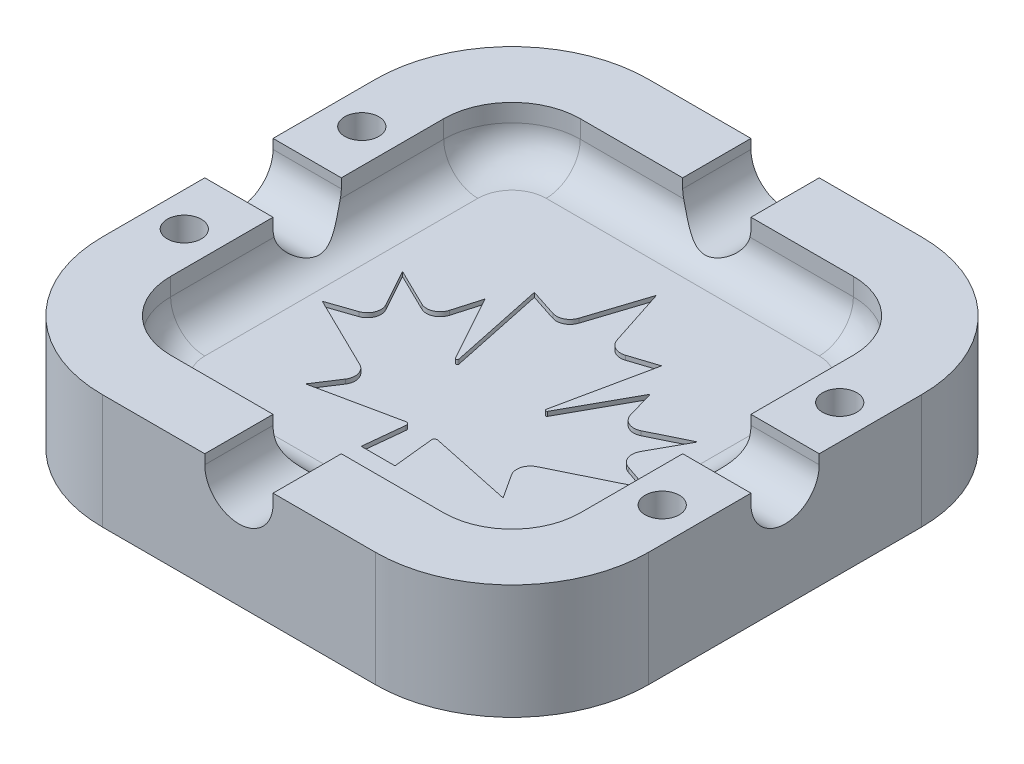
SolidWorks part; units mm, degrees
ref_plane "Front" through (0, 0, 0) normal (0, 0, 1) x (1, 0, 0)
ref_plane "Top" through (0, 0, 0) normal (0, 1, 0) x (1, 0, 0)
ref_plane "Side" through (0, 0, 0) normal (1, 0, 0) x (0, 0, -1)
sketch "MCAM Cord system" plane through (0, 0, 0) normal (0, 0, 1) x (1, 0, 0)
  line L0 (0, 0) -> (0, 32.3125) construction
  line L1 (0, 0) -> (36.1919, 0) construction
sketch "Sketch1" plane through (0, 0, 0) normal (0, 1, 0) x (1, 0, 0)
  line L0 (-25.4, 25.4) -> (25.4, -25.4) construction
  line L1 (-25.4, 25.4) -> (25.4, 25.4)
  line L2 (-25.4, 25.4) -> (-25.4, -25.4)
  line L3 (-25.4, -25.4) -> (25.4, -25.4)
  line L4 (25.4, 25.4) -> (25.4, -25.4)
  point P12 (25.4, 25.4)
  dimension "D2" = 50.8
  dimension "D1" = 50.8
extrude "Boss-Extrude1" add sketch "Sketch1" against normal blind 10.668
sketch "Sketch3" plane through (0, 0, 0) normal (0, 1, 0) x (1, 0, 0)
  line L8 (19.05, -19.05) -> (19.05, 19.05)
  line L9 (19.05, 19.05) -> (-19.05, 19.05)
  line L10 (-19.05, 19.05) -> (-19.05, -19.05)
  line L11 (-19.05, -19.05) -> (19.05, -19.05)
  line L12 (19.05, -12.7) -> (19.05, 12.7)
  line L13 (12.7, 19.05) -> (-12.7, 19.05)
  line L14 (-19.05, 12.7) -> (-19.05, -12.7)
  line L15 (-12.7, -19.05) -> (12.7, -19.05)
  arc A4 (-19.05, -12.7) -> (-12.7, -19.05) centre (-12.7, -12.7) ccw
  arc A5 (19.05, -12.7) -> (12.7, -19.05) centre (12.7, -12.7) cw
  arc A6 (19.05, 12.7) -> (12.7, 19.05) centre (12.7, 12.7) ccw
  arc A7 (-12.7, 19.05) -> (-19.05, 12.7) centre (-12.7, 12.7) ccw
  dimension "D2" = 6.35
  dimension "D1" = 6.35
extrude "Cut-Extrude2" cut sketch "Sketch3" against normal blind 4.826
fillet "Fillet2" radius 12.7 4 edges at (25.4, -5.334, -25.4) (25.4, -5.334, 25.4) (-25.4, -5.334, 25.4) (-25.4, -5.334, -25.4)
fillet "Fillet1" radius 3.175 8 edges at (17.1901, -4.826, -17.1901) (19.05, -4.826, 0) (17.1901, -4.826, 17.1901) (0, -4.826, 19.05) (-17.1901, -4.826, 17.1901) (-19.05, -4.826, 0) (-17.1901, -4.826, -17.1901) (0, -4.826, -19.05)
sketch "Sketch4" plane through (0, 0, 0) normal (1, 0, 0) x (0, 0, -1)
  line L2 (-3.175, -0.889) -> (-3.175, 0)
  line L4 (-12.7, 0) -> (12.7, 0) construction
  line L5 (3.175, -0.889) -> (3.175, 0)
  line L6 (3.175, 0) -> (-3.175, 0)
  line L7 (0, -4.064) -> (7.4473, -4.064) construction
  arc A0 (-3.175, -0.889) -> (3.175, -0.889) centre (0, -0.889) ccw
  dimension "D1" = 4.064
  dimension "D2" = 6.35
extrude "Cut-Extrude3" cut sketch "Sketch4" against normal mid plane 59.944
ref_axis "Axis1" through (0, 50, 0) along (0, -1, 0)
pattern_circular "CirPattern1" count 4 over 360 about axis through (0, 50, 0) along (0, -1, 0) of "Cut-Extrude3"
sketch "Sketch5" plane through (0, -4.826, 0) normal (0, 1, 0) x (1, 0, 0)
  text T0 "UWO\r\nUMS"
extrude "Cut-Extrude4 UWO UMS engrave" [suppressed] cut sketch "Sketch5" against normal blind 0.7874
hole_wizard "1/8 (0.125) Diameter Hole1" positions "Sketch7" profile "Sketch6" hole size "1/8" standard "ANSI Inch"
sketch "Sketch7" plane through (0, 0, 0) normal (0, 1, 0) x (-1, 0, 0)
  line L2 (0, 0) -> (35.8085, 0) construction
  line L4 (0, 0) -> (0, -33.2213) construction
  line L5 (25.4, -12.7) -> (25.4, -3.175) construction
  line L6 (25.4, -3.175) -> (19.05, -3.175) construction
  point P0 (22.225, -8.255)
  point P21 (22.225, 8.255)
  point P23 (-22.225, 8.255)
  point P24 (-22.225, -8.255)
  dimension "D1" = 3.175
  dimension "D2" = 5.08
sketch "Sketch6" plane through (-22.225, 0, -8.255) normal (1, 0, 0) x (0, 0, 1)
  line L0 (0, 0) -> (0, 5.2719)
  line L1 (0, 5.2719) -> (1.5875, 4.318)
  line L2 (1.5875, 4.318) -> (1.5875, 0)
  line L5 (1.5875, 0) -> (0, 0)
  line L10 (0, 5.2719) -> (-1.5875, 4.318) construction
  line L11 (0, -6.35) -> (0, 107.95) construction
  dimension "Hole Dia." = 3.175
  dimension "Hole Depth" = 4.318
  dimension "Drill Angle" = 118
sketch "Sketch9" plane through (0, -4.826, 0) normal (0, 1, 0) x (1, 0, 0)
  line L0 (0.246, 15.3092) -> (0.246, -18.2427) construction
  line L1 (0.246, 13.1897) -> (-1.5247, 7.7402)
  line L2 (-12.7, -25.4) -> (-3.175, -25.4) construction
  line L3 (-3.125, 6.9248) -> (-5.6734, 7.7528)
  line L4 (-5.6734, 7.7528) -> (-3.8057, -1.1208)
  line L5 (-4.0412, -1.2084) -> (-7.4307, 4.9339)
  line L6 (-7.4307, 4.9339) -> (-8.1741, 2.3596)
  line L7 (-9.9532, 1.5716) -> (-13.4884, 3.3041)
  line L8 (-13.4884, 3.3041) -> (-11.5862, -0.1428)
  line L9 (-12.287, -1.958) -> (-14.8221, -2.8256)
  line L10 (-14.8221, -2.8256) -> (-7.9797, -6.1789)
  line L11 (-7.4748, -8.0131) -> (-8.9384, -10.2575)
  line L12 (-8.9384, -10.2575) -> (-1.2332, -8.6358)
  line L13 (-0.9283, -8.9109) -> (-1.3265, -12.7)
  line L14 (-1.3265, -12.7) -> (1.8185, -12.7)
  line L15 (1.4202, -8.9109) -> (1.8185, -12.7)
  line L16 (9.4303, -10.2575) -> (1.7251, -8.6358)
  line L17 (7.9667, -8.0131) -> (9.4303, -10.2575)
  line L18 (15.3141, -2.8256) -> (8.4716, -6.1789)
  line L19 (12.7789, -1.958) -> (15.3141, -2.8256)
  line L20 (13.9803, 3.3041) -> (12.0782, -0.1428)
  line L21 (10.4451, 1.5716) -> (13.9803, 3.3041)
  line L22 (7.9226, 4.9339) -> (8.6661, 2.3596)
  line L23 (4.5331, -1.2084) -> (7.9226, 4.9339)
  line L24 (6.1653, 7.7528) -> (4.2976, -1.1208)
  line L25 (3.6169, 6.9248) -> (6.1653, 7.7528)
  line L26 (0.246, 13.1897) -> (2.0166, 7.7402)
  arc A0 (-1.5247, 7.7402) -> (-3.125, 6.9248) centre (-2.7325, 8.1326) cw
  arc A1 (-7.9797, -6.1789) -> (-7.4748, -8.0131) centre (-8.5386, -7.3193) cw
  arc A2 (-11.5862, -0.1428) -> (-12.287, -1.958) centre (-12.6982, -0.7564) cw
  arc A3 (-8.1741, 2.3596) -> (-9.9532, 1.5716) centre (-9.3943, 2.712) cw
  arc A4 (-3.8057, -1.1208) -> (-4.0412, -1.2084) centre (-3.93, -1.147) cw
  arc A5 (-0.9283, -8.9109) -> (-1.2332, -8.6358) centre (-1.1809, -8.8843) ccw
  arc A6 (1.4202, -8.9109) -> (1.7251, -8.6358) centre (1.6728, -8.8843) cw
  arc A7 (4.2976, -1.1208) -> (4.5331, -1.2084) centre (4.4219, -1.147) ccw
  arc A8 (8.6661, 2.3596) -> (10.4451, 1.5716) centre (9.8862, 2.712) ccw
  arc A9 (12.0782, -0.1428) -> (12.7789, -1.958) centre (13.1901, -0.7564) ccw
  arc A10 (8.4716, -6.1789) -> (7.9667, -8.0131) centre (9.0305, -7.3193) ccw
  arc A11 (2.0166, 7.7402) -> (3.6169, 6.9248) centre (3.2245, 8.1326) ccw
  point P17 (-1.9172, 6.5323)
  point P51 (0.246, -12.7)
  point P56 (2.4091, 6.5323)
  dimension "D6" = 1.27
  dimension "D7" = 1.27
  dimension "D8" = 1.27
  dimension "D9" = 1.27
  dimension "D10" = 0.127
  dimension "D11" = 0.254
  dimension "D1" = 18
  dimension "D2" = 7
  dimension "D3" = 80
  dimension "D4" = 80
  dimension "D5" = 35
  dimension "D12" = 12.7
  dimension "D13" = 6
  dimension "D14" = 3.81
  dimension "D15" = 7.874
  dimension "D16" = 83
extrude "Cut-Extrude4" cut sketch "Sketch9" against normal blind 0.4064
sketch "Sketch20" plane through (0, -10.668, 0) normal (0, -1, 0) x (-1, 0, 0)
  line L0 (-18.5358, -7.366) -> (18.5358, -7.366) construction
  line L1 (-8.4009, 7.4831) -> (-5.7011, 16.3751)
  line L2 (-9.2516, 6.8524) -> (9.1902, 6.8524) construction
  line L3 (-9.0426, -20.32) -> (9.0426, -20.32) construction
  line L4 (0, -20.32) -> (0, -7.366) construction
  line L22 (12.7, -25.4) -> (-12.7, -25.4) construction
  line L23 (-5.7011, 16.3751) -> (-3.0053, 7.4766)
  line L25 (-1.2647, 7.7348) -> (-1.2647, 19.431)
  line L26 (0, -20.32) -> (0, -25.4) construction
  line L27 (-3.0427, 19.431) -> (-3.0447, 13.7331)
  line L28 (-3.0447, 13.7331) -> (-4.854, 19.6957)
  line L29 (-6.5513, 19.6958) -> (-8.3605, 13.7331)
  line L30 (-8.3605, 13.7331) -> (-8.3605, 19.4377)
  line L31 (-10.1385, 19.4377) -> (-10.1406, 7.7415)
  line L32 (9.1908, 8.6304) -> (3.1034, 8.6325)
  line L33 (3.1034, 8.6325) -> (3.1048, 12.7026)
  line L34 (3.1048, 12.7026) -> (9.1923, 12.7005)
  line L35 (9.1929, 14.4785) -> (3.1054, 14.4806)
  line L36 (3.1054, 14.4806) -> (3.1069, 18.542)
  line L37 (3.1069, 18.542) -> (9.1301, 18.542)
  line L38 (9.1301, 20.32) -> (1.8788, 20.32)
  line L39 (1.2338, 19.6718) -> (1.2955, 7.4941)
  line L40 (1.9405, 6.8524) -> (9.1902, 6.8524)
  line L41 (-1.2647, 13.5829) -> (1.2647, 13.5829) construction
  line L42 (0, 13.5829) -> (0, 0) construction
  line L43 (-9.2495, 20.32) -> (9.1301, 20.32) construction
  line L44 (1.2338, 20.32) -> (1.2338, 25.4) construction
  line L45 (-12.7, 25.4) -> (12.7, 25.4) construction
  arc A0 (-3.0053, 7.4766) -> (-1.2647, 7.7348) centre (-2.1537, 7.7317) ccw
  arc A11 (-1.2647, 19.431) -> (-3.0427, 19.431) centre (-2.1537, 19.431) ccw
  arc A12 (-4.854, 19.6957) -> (-6.5513, 19.6958) centre (-5.7027, 19.431) ccw
  arc A13 (-8.3605, 19.4377) -> (-10.1385, 19.4377) centre (-9.2495, 19.431) ccw
  arc A14 (-10.1406, 7.7415) -> (-8.4009, 7.4831) centre (-9.2516, 7.7414) ccw
  arc A15 (9.1902, 6.8524) -> (9.1908, 8.6304) centre (9.1905, 7.7414) ccw
  arc A16 (9.1923, 12.7005) -> (9.1929, 14.4785) centre (9.1926, 13.5895) ccw
  arc A17 (9.1301, 18.542) -> (9.1301, 20.32) centre (9.1301, 19.431) ccw
  arc A18 (1.8788, 20.32) -> (1.2338, 19.6718) centre (1.8788, 19.675) ccw
  arc A19 (1.2955, 7.4941) -> (1.9405, 6.8524) centre (1.9405, 7.4973) ccw
  text T0 "<b>2024</b>" font "Arial" height in points 50
  text T1 "<b>9</b>" font "Century Gothic" height in points 40
  point P57 (-5.7026, 20.32)
  point P58 (-2.1537, 20.32)
  point P59 (-2.0232, 6.8524)
  point P61 (-18.5358, -7.366)
  dimension "D4" = 12.954
  dimension "D2" = 5.08
  dimension "D1" = 13.4676
extrude "Cut-Extrude9" cut sketch "Sketch20" against normal blind 0.381
